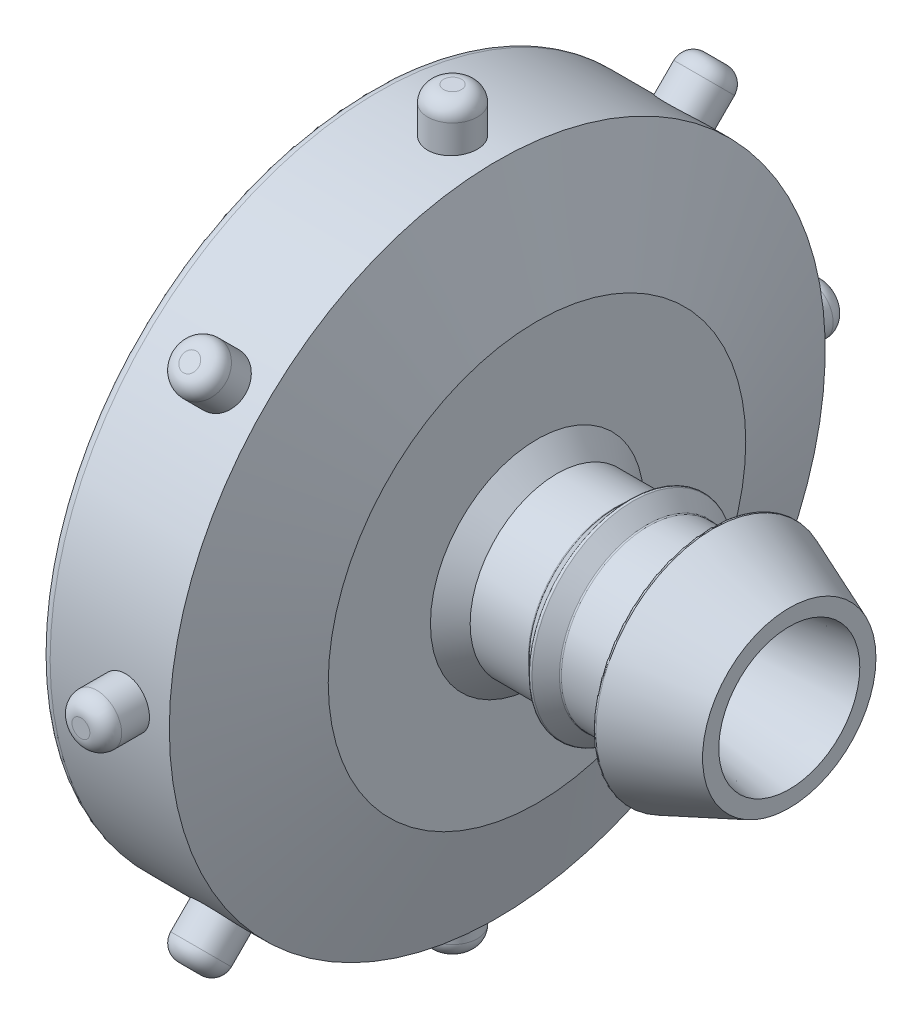
SolidWorks part; units mm, degrees
note: The reader was unsure of these and kept them because the rebuilt part matched: shared geometry of "Sketch2<5>", "Sketch2<6>".
ref_plane "Front Plane" through (0, 0, 0) normal (0, 0, 1) x (1, 0, 0)
ref_plane "Top Plane" through (0, 0, 0) normal (0, 1, 0) x (1, 0, 0)
ref_plane "Right Plane" through (0, 0, 0) normal (1, 0, 0) x (0, 0, -1)
sketch "Sketch1" plane through (0, 0, 0) normal (0, 1, 0) x (1, 0, 0)
  line L0 (0, 0) -> (-12.7, 0)
  line L1 (0, 0) -> (0, 4.365)
  line L2 (0, 4.365) -> (-3.97, 5.955)
  line L3 (-3.97, 5.955) -> (-3.97, 4.365)
  line L4 (0, 4.365) -> (-19.3321, 4.365) construction
  line L5 (-3.97, 4.365) -> (-7.15, 4.365)
  line L6 (-7.15, 4.365) -> (-7.94, 5.155)
  line L7 (-7.94, 5.155) -> (-8.73, 4.365)
  line L8 (-8.73, 4.365) -> (-12.7, 4.365)
  line L9 (-12.7, 4.365) -> (-12.7, 0)
  dimension "D1" = 12.7
  dimension "D2" = 4.365
  dimension "D3" = 1.59
  dimension "D4" = 3.97
  dimension "D5" = 7.94
  dimension "D6" = 0.79
revolve "Revolve1" add sketch "Sketch1" angle 360 about L0
sketch "Sketch2" plane through (-12.7, 0, 0) normal (-1, 0, 0) x (0, 0, 1)
  line L0 (1.23, 2.175) -> (1.23, -2.175) construction
  line L1 (-8.9, 6.9) -> (8.9, 6.9) construction
  line L2 (-8.9, 6.9) -> (-8.9, -5.8) construction
  line L3 (-8.9, -5.8) -> (8.9, -5.8) construction
  line L4 (8.9, 6.9) -> (8.9, -5.8) construction
  line L7 (1.23, -2.175) -> (-1.23, -2.175) construction
  line L8 (-1.23, -2.175) -> (-1.23, 2.175) construction
  line L9 (-1.23, 2.175) -> (1.23, 2.175) construction
  line L10 (0, 6.9) -> (0, -5.8) construction
  line L17 (-1.23, 2.175) -> (1.23, -2.175) construction
  line L18 (-8.9, -5.8) -> (8.9, -5.8)
  line L19 (-8.9, -5.8) -> (-8.9, -4)
  line L20 (-8.9, -4) -> (8.9, -4)
  line L21 (8.9, -5.8) -> (8.9, -4)
  line L22 (-8.9, -5.8) -> (8.9, -4) construction
  line L23 (-8.9, -4) -> (8.9, -5.8) construction
  line L28 (-9.4, 7.1) -> (9.4, 7.1)
  line L29 (-9.4, 7.1) -> (-9.4, -6.3)
  line L30 (-9.4, -6.3) -> (9.4, -6.3)
  line L31 (9.4, 7.1) -> (9.4, -6.3)
  line L32 (-9.4, 7.1) -> (9.4, -6.3) construction
  line L33 (-9.4, -6.3) -> (9.4, 7.1) construction
  line L34 (1.23, 2.175) -> (-1.23, -2.175) construction
  circle A0 centre (-6.5, 4.05) radius 0.95
  circle A1 centre (6.5, 4.05) radius 0.95
  circle A2 centre (0, 0) radius 2.55
  circle A3 centre (0, 0) radius 16.51
  point P0 (0, 0)
  point P8 (-4.5814, -3.5103)
  point P25 (0, -4.9)
  point P30 (0, 0)
  point P31 (0, 0)
  point P35 (0, 0.4)
  circle M5 centre (0, 0) radius 4.365
  dimension "D9" = 1.9
  dimension "D10" = 2.85
  dimension "D11" = 2.4
  dimension "D12" = 5.1
  dimension "D18" = 33.02
  dimension "D1" = 12.7
  dimension "D2" = 17.8
  dimension "D3" = 7.67
  dimension "D4" = 6.9
  dimension "D5" = 2.46
  dimension "D6" = 4.35
  dimension "D13" = 1.8
  dimension "D14" = 0.5
  dimension "D15" = 0.5
  dimension "D16" = 0.2
  dimension "D17" = 0.5
extrude "Boss-Extrude1" add sketch "Sketch2" along normal blind 1.5 contours A3 L28 L31 L30 L29 | L31 L28 L29 L30 L21 L18 L19 L20 A0 A1 M5 | A0 | A1 | L20 A2 M5 | L18 L21 L20 L19 M5 | L20 M5 | A2
extrude "Cut-Extrude1" cut sketch "Sketch2<5>" against normal through all and the other way through all contours A2 L8 L9 L0 L7 | L9 L8 L7 L0
sketch "Sketch2<5>" plane through (-12.7, 0, 0) normal (-1, 0, 0) x (0, 0, 1) same geometry as "Sketch2"
extrude "Boss-Extrude4" add sketch "Sketch2<6>" along normal offset from surface (8.5 mm away) 7 contours A3 L28 L31 L30 L29 up to face at (-14.2, 0, 2.55) offset beyond the face yes
sketch "Sketch2<6>" plane through (-12.7, 0, 0) normal (-1, 0, 0) x (0, 0, 1) same geometry as "Sketch2"
sketch "Sketch8" plane through (-21.2, 0, 0) normal (-1, 0, 0) x (0, 0, 1)
  circle A0 centre (0, 0) radius 14.1414
  dimension "D1" = 28.2829
sweep "Cut-Sweep1" cut path "Sketch8" circular profile diameter 1.8 parameters "D3"=1.8
ref_plane "Plane1" through (0, -16.51, 0) normal (0, -1, 0) x (-1, 0, 0)
chamfer "Chamfer1" distance 6 distance2 2 1 edges at (-12.7, 0, 16.51)
sketch "Sketch18" plane through (-14.2, 0, 0) normal (-1, 0, 0) x (0, 0, 1)
  line L1 (-9.4, -6.3) -> (-5.9, -6.3)
  line L2 (-9.4, -6.3) -> (-9.4, 1.35)
  line L3 (-9.4, 1.35) -> (-5.9, 1.35)
  line L4 (-5.9, -6.3) -> (-5.9, 1.35)
  line L5 (-9.4, -6.3) -> (-5.9, 1.35) construction
  line L6 (-9.4, 1.35) -> (-5.9, -6.3) construction
  point P4 (-7.65, -2.475)
  dimension "D1" = 7.65
  dimension "D2" = 3.5
extrude "Boss-Extrude7" add sketch "Sketch18" along normal blind 0.64
fillet "Fillet7" radius 0.5 2 edges at (-14.84, 1.35, -7.65) (-14.84, -2.475, -5.9)
sketch "Sketch20" plane through (0, 0, 0) normal (0, 0, 1) x (1, 0, 0)
  line L0 (-21.2, -16.51) -> (-21.2, 16.51) construction
  arc A0 (-20.3, -14.1414) -> (-21.2, -13.2414) centre (-21.2, -14.1414) ccw construction
  arc A1 (-21.2, 13.2414) -> (-20.3, 14.1414) centre (-21.2, 14.1414) ccw construction
  point P4 (-21.2, -13.2414)
  point P5 (-21.2, -6.3)
  point P9 (-21.2, 13.2414)
  point P14 (-21.2, 7.1)
fillet "Fillet8" radius 1 1 edges at (-21.2, 0, 15.0415)
chamfer "Chamfer5" distance 1 distance2 4 1 edges at (-21.2, -6.3, 0)
fillet "Fillet9" radius 0.5 1 edges at (-21.2, 0, 16.51)
fillet "Fillet10" radius 0.1 5 edges at (-3.97, 0, -5.955) (-3.97, 0, -4.365) (-7.15, 0, -4.365) (-8.73, 0, -4.365) (-7.94, 0, -5.155)
sketch "Sketch42" plane through (0, -16.51, 0) normal (0, -1, 0) x (-1, 0, 0)
  line L0 (21.2, 0) -> (12.7, 0)
  line L5 (12.7, 10.51) -> (12.7, -10.51) construction
  circle A0 centre (16.95, 0) radius 1.25
  dimension "D1" = 2.5
extrude "Boss-Extrude8" add sketch "Sketch42" along normal blind 2.2 and the other way blind 2 contours L0 A0 | L0 A0
fillet "Fillet11" radius 0.8 1 edges at (-16.95, -18.71, -1.25)
pattern_circular "CirPattern4" count 8 over 360 about axis through (0, 0, 0) along (1, 0, 0) of "Boss-Extrude8", "Fillet11"
chamfer "Chamfer7" distance 1 angle 45 1 edges at (-12.7, 0, -4.365)
chamfer "Chamfer8" distance 7 distance2 1 1 edges at (0, 0, 2.55)
equation "\"WallThick\"= 1.2'thickness of wall for printer"
equation "\"dHole\"= 3.3'diameter of screw hole"
